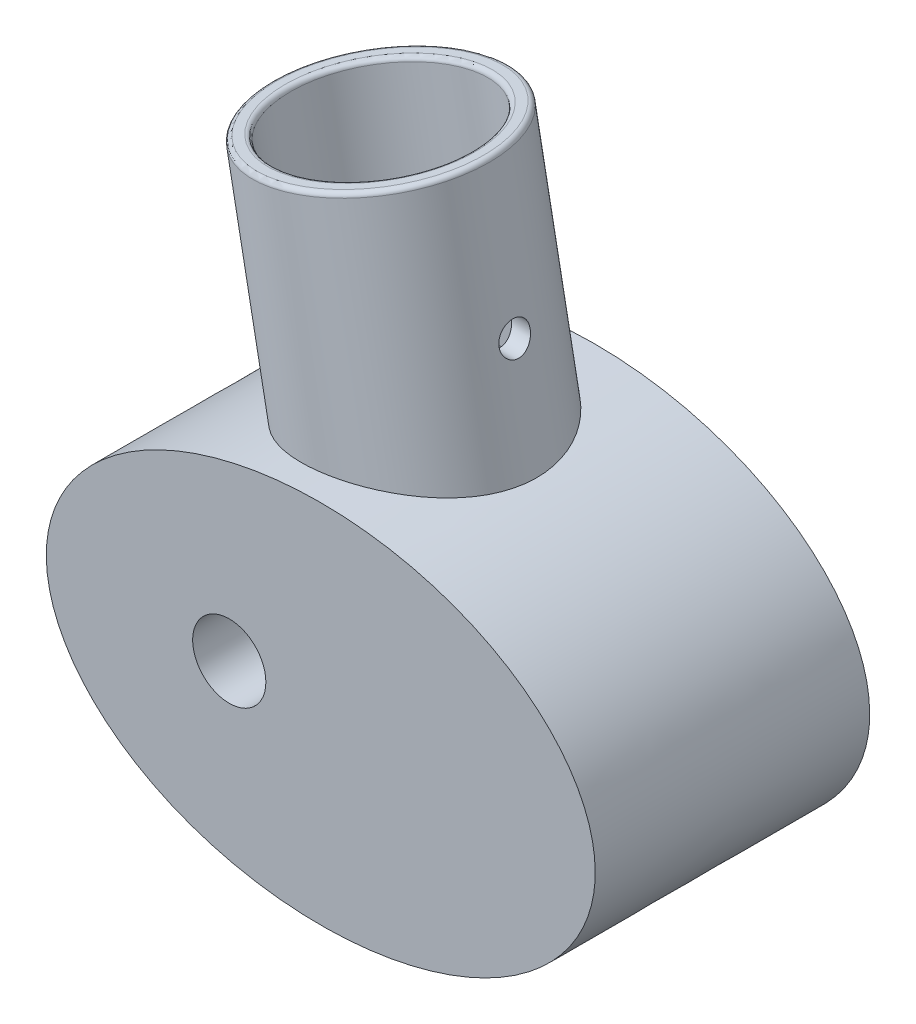
SolidWorks part; units mm, degrees
ref_plane "Front Plane" through (0, 0, 0) normal (0, 0, 1) x (1, 0, 0)
ref_plane "Top Plane" through (0, 0, 0) normal (0, 1, 0) x (1, 0, 0)
ref_plane "Right Plane" through (0, 0, 0) normal (1, 0, 0) x (0, 0, -1)
sketch "Sketch2" plane through (0, 0, 0) normal (0, 0, 1) x (1, 0, 0)
  line L102 (-3.3983, 10.2) -> (7.0395, 10.2) construction
  line L103 (7.0395, 10.2) -> (29.1, 10.2) construction
  line L104 (30.1, 9.2) -> (30.1, 0.75) construction
  line L105 (31.7, 0.75) -> (30.1, 0.75) construction
  line L106 (31.7, 0.75) -> (35.9, 0.75) construction
  line L107 (35.9, 0.75) -> (35.9, -0.75) construction
  line L108 (35.9, -0.75) -> (30.1, -0.75) construction
  line L109 (30.1, -0.75) -> (30.1, -9.2) construction
  line L110 (29.1, -10.2) -> (7.0395, -10.2) construction
  line L111 (7.0395, -10.2) -> (-3.3983, -10.2) construction
  line L112 (-3.3983, -10.2) -> (-9.1, -10.2) construction
  line L113 (-11.7, -0.75) -> (-10.1, -0.75) construction
  line L114 (-11.7, -0.75) -> (-15.9, -0.75) construction
  line L115 (-15.9, -0.75) -> (-15.9, 0.75) construction
  line L116 (-15.9, 0.75) -> (-11.7, 0.75) construction
  line L117 (-10.1, 0.75) -> (-11.7, 0.75) construction
  line L118 (-10.1, -9.2) -> (-10.1, -0.75) construction
  line L119 (-10.1, 0.75) -> (-10.1, 9.2) construction
  line L120 (-9.1, 10.2) -> (-3.3983, 10.2) construction
  line L121 (-3.3983, 10.6) -> (7.0395, 10.6)
  line L122 (7.0395, 10.6) -> (29.1, 10.6)
  line L123 (30.5, 9.2) -> (30.5, 1.15)
  line L124 (31.7, 1.15) -> (30.5, 1.15)
  line L125 (31.7, 1.15) -> (36.3, 1.15)
  line L126 (36.3, 1.15) -> (36.3, -1.15)
  line L127 (36.3, -1.15) -> (30.5, -1.15)
  line L128 (30.5, -1.15) -> (30.5, -9.2)
  line L129 (29.1, -10.6) -> (7.0395, -10.6)
  line L130 (7.0395, -10.6) -> (-3.3983, -10.6)
  line L131 (-3.3983, -10.6) -> (-9.1, -10.6)
  line L132 (-10.5, -9.2) -> (-10.5, -1.15)
  line L133 (-11.7, -1.15) -> (-10.5, -1.15)
  line L134 (-11.7, -1.15) -> (-16.3, -1.15)
  line L135 (-16.3, -1.15) -> (-16.3, 1.15)
  line L136 (-16.3, 1.15) -> (-11.7, 1.15)
  line L137 (-10.5, 1.15) -> (-11.7, 1.15)
  line L138 (-10.5, 1.15) -> (-10.5, 9.2)
  line L139 (-9.1, 10.6) -> (-3.3983, 10.6)
  arc A20 (30.1, 9.2) -> (29.1, 10.2) centre (29.1, 9.2) ccw construction
  arc A21 (29.1, -10.2) -> (30.1, -9.2) centre (29.1, -9.2) ccw construction
  arc A22 (-10.1, -9.2) -> (-9.1, -10.2) centre (-9.1, -9.2) ccw construction
  arc A23 (-9.1, 10.2) -> (-10.1, 9.2) centre (-9.1, 9.2) ccw construction
  arc A24 (30.5, 9.2) -> (29.1, 10.6) centre (29.1, 9.2) ccw
  arc A25 (29.1, -10.6) -> (30.5, -9.2) centre (29.1, -9.2) ccw
  arc A26 (-10.5, -9.2) -> (-9.1, -10.6) centre (-9.1, -9.2) ccw
  arc A27 (-9.1, 10.6) -> (-10.5, 9.2) centre (-9.1, 9.2) ccw
  ellipse E0 centre (10, 0) end of major axis (40, 0) minor radius 20
  dimension "D2" = 60
  dimension "D3" = 40
  dimension "D4" = 10
  dimension "D1" = 0.4
extrude "Boss-Extrude1" add sketch "Sketch2" along normal blind 30 contours E0 region at (-19.2789, -0.0201, 0)
sketch "Sketch3" plane through (0, 0, 0) normal (0, 0, -1) x (-1, 0, 0)
  arc A0 (-36.8729, -5.875) -> (-36.8729, -4.125) centre (-34.8, -5) ccw construction
  arc A1 (-36.8729, 4.125) -> (-36.8729, 5.875) centre (-34.8, 5) ccw construction
  arc A2 (16.8729, 5.875) -> (16.8729, 4.125) centre (14.8, 5) ccw construction
  arc A3 (16.8729, -4.125) -> (16.8729, -5.875) centre (14.8, -5) ccw construction
  arc A4 (-36.8729, -5.875) -> (-36.8729, -4.125) centre (-34.8, -5) ccw construction
  arc A5 (-36.8729, 4.125) -> (-36.8729, 5.875) centre (-34.8, 5) ccw construction
  arc A6 (16.8729, 5.875) -> (16.8729, 4.125) centre (14.8, 5) ccw construction
  arc A7 (16.8729, -4.125) -> (16.8729, -5.875) centre (14.8, -5) ccw construction
  arc A8 (16.8729, -5.875) -> (16.8729, -4.125) centre (14.8, -5) ccw construction
  arc A9 (16.8729, 4.125) -> (16.8729, 5.875) centre (14.8, 5) ccw construction
  arc A10 (-36.8729, 5.875) -> (-36.8729, 4.125) centre (-34.8, 5) ccw construction
  arc A11 (-36.8729, -4.125) -> (-36.8729, -5.875) centre (-34.8, -5) ccw construction
  arc A12 (-35.9516, -5.4861) -> (-35.9516, -4.5139) centre (-34.8, -5) ccw
  arc A13 (-35.9516, -4.5139) -> (-35.9516, -5.4861) centre (-34.8, -5) ccw
  arc A14 (-35.9516, 4.5139) -> (-35.9516, 5.4861) centre (-34.8, 5) ccw
  arc A15 (-35.9516, 5.4861) -> (-35.9516, 4.5139) centre (-34.8, 5) ccw
  arc A16 (15.9516, 5.4861) -> (15.9516, 4.5139) centre (14.8, 5) ccw
  arc A17 (15.9516, 4.5139) -> (15.9516, 5.4861) centre (14.8, 5) ccw
  arc A18 (15.9516, -4.5139) -> (15.9516, -5.4861) centre (14.8, -5) ccw
  arc A19 (15.9516, -5.4861) -> (15.9516, -4.5139) centre (14.8, -5) ccw
  dimension "D1" = 1.25
extrude "Cut-Extrude1" cut sketch "Sketch3" against normal blind 3
ref_plane "Plane3" through (10, 0, 0) normal (1, 0, 0) x (0, 0, -1)
sketch "Sketch16" plane through (10, 0, 0) normal (1, 0, 0) x (0, 0, -1)
  line L0 (0, 0) -> (50000, 0) construction
ref_plane "Plane6" through (9.648, 1.8427, 0) normal (-0.9822, -0.1876, 0) x (0, 0, -1)
sketch "Sketch6" plane through (11.1721, -6.137, 0) normal (-0.9822, -0.1876, 0) x (-0.1876, 0.9822, 0)
  line L1 (26.6831, 0) -> (-14.1873, 0) construction
  line L3 (-14.1873, -30) -> (26.6831, -30) construction
  line L7 (26.6831, -15) -> (51.6831, -15)
  line L8 (26.6831, 0) -> (-14.1873, 0) construction
  line L9 (-14.1873, -30) -> (26.6831, -30) construction
  line L10 (26.6831, 0) -> (26.6831, -30) construction
  dimension "D1" = 25
ref_plane "Plane1" through (1.4762, 44.6285, 15) normal (-0.1876, 0.9822, 0) x (0.9822, 0.1876, 0)
sketch "Sketch7" plane through (1.4762, 44.6285, 15) normal (-0.1876, 0.9822, 0) x (0.9822, 0.1876, 0)
  circle A0 centre (0, 0) radius 10.05
  circle A1 centre (0, 0) radius 12.05
  point P12 (0, 0)
  dimension "D1" = 20.1
  dimension "D2" = 2
extrude "Boss-Extrude2" add sketch "Sketch7" against normal up to body
sketch "Sketch8" plane through (0, 0, 30) normal (0, 0, 1) x (1, 0, 0)
  line L0 (10, 0) -> (10, -3.4904) construction
  ellipse E0 centre (10, 0) end of major axis (40, 0) minor radius 20 construction
  ellipse E1 centre (10, 0) end of major axis (40, 0) minor radius 20
extrude "Boss-Extrude4" add sketch "Sketch8" against normal up to surface (7.4 mm away)
sketch "Sketch12" plane through (10, -10, 0) normal (-1, 0, 0) x (0, 1, 0)
  line L6 (30, -30) -> (30, 0) construction
  line L7 (30, -15) -> (52.3679, -15) construction
  circle A0 centre (41.1839, -15) radius 1.7
  ellipse E0 centre (54.6285, -15) end of major axis (54.6285, -2.95) minor radius 2.2606 construction
  dimension "D1" = 3.4
extrude "Cut-Extrude3" cut sketch "Sketch12" against normal through all both and the other way through all
sketch "Sketch15" [suppressed] plane through (10, 0, 0) normal (1, 0, 0) x (0, 0, -1)
  line L0 (0, 0) -> (50000, 0) construction
  line L1 (0, -20) -> (0, 20) construction
  point P4 (0, 0)
ref_plane "Plane4" [suppressed] through (9.4211, -2.3354, 0) normal (0.9706, -0.2406, 0) x (0, 0, -1)
sketch "Sketch9" [suppressed] plane through (12.5635, 10.3412, 0) normal (0.9706, -0.2406, 0) x (-0.2406, -0.9706, 0)
  line L0 (31.3652, -30) -> (31.3652, 0) construction
  line L1 (31.3652, -30) -> (31.3652, 0) construction
  line L2 (31.3652, -15) -> (55.6745, -9.1639)
  dimension "D1" = 25
  dimension "D2" = 13.5
ref_plane "Plane2" [suppressed] through (-0.8323, -43.6977, 9.1639) normal (-0.234, -0.9438, -0.2334) x (-0.4258, 0.3153, -0.8481)
sketch "Sketch10" [suppressed] plane through (-0.8323, -43.6977, 9.1639) normal (-0.234, -0.9438, -0.2334) x (-0.4258, 0.3153, -0.8481)
  line L0 (-12.7213, -7.1349) -> (12.7213, 7.1349) construction
  circle A0 centre (0, 0) radius 10.05
  circle A1 centre (0, 0) radius 12.05
  dimension "D1" = 20.1
  dimension "D2" = 2
extrude "Boss-Extrude5" [suppressed] add sketch "Sketch10" against normal up to surface (28.0273 mm away) up to face at (18.3615, 19.2075, 12.639)
sketch "Sketch11" [suppressed] plane through (12.5635, 10.3412, 0) normal (0.9706, -0.2406, 0) x (-0.2406, -0.9706, 0)
  line L2 (31.3652, 0) -> (31.3652, -30) construction
  line L3 (31.3652, -15) -> (55.6745, -9.1639) construction
  line L4 (58.0206, -18.9362) -> (53.3283, 0.6085) construction
  circle A1 centre (43.5198, -12.0819) radius 1.7
  dimension "D1" = 3.4
extrude "Cut-Extrude2" [suppressed] cut sketch "Sketch11" against normal through all both and the other way through all
sketch "Sketch13" plane through (0, 0, 30) normal (0, 0, 1) x (1, 0, 0)
  circle A0 centre (0, 0) radius 4
  dimension "D1" = 8
extrude "Cut-Extrude4" cut sketch "Sketch13" against normal through all both and the other way through all
sketch "Sketch14" [suppressed] plane through (0, 0, 30) normal (0, 0, 1) x (1, 0, 0)
  circle A1 centre (20, 0) radius 4
  ellipse E3 centre (10, 0) end of major axis (40, 0) minor radius 20
  ellipse E4 centre (10, 0) end of major axis (40, 0) minor radius 20
  dimension "D1" = 8
  dimension "D3" = 10
  dimension "D2" = 0
extrude "Cut-Extrude5" [suppressed] cut sketch "Sketch14" against normal through all both and the other way through all contours A1
ref_plane "Plane5" [suppressed] through (-25, 0, 0) normal (1, 0, 0) x (0, 0, -1)
mirror "Mirror1" [suppressed] about plane through (-25, 0, 0) normal (1, 0, 0) of bodies 112 113
delete or keep bodies "Body-Delete/Keep 1" [suppressed] type delete bodies bodies 112
fillet "Fillet1" [suppressed] radius 0.5
fillet "Fillet2" [suppressed] radius 0.5
fillet "Fillet3" radius 0.5 2 edges at (-10.3599, 42.3679, 15) (-8.3954, 42.7431, 15)
fillet "Fillet4" [suppressed] radius 0.5
